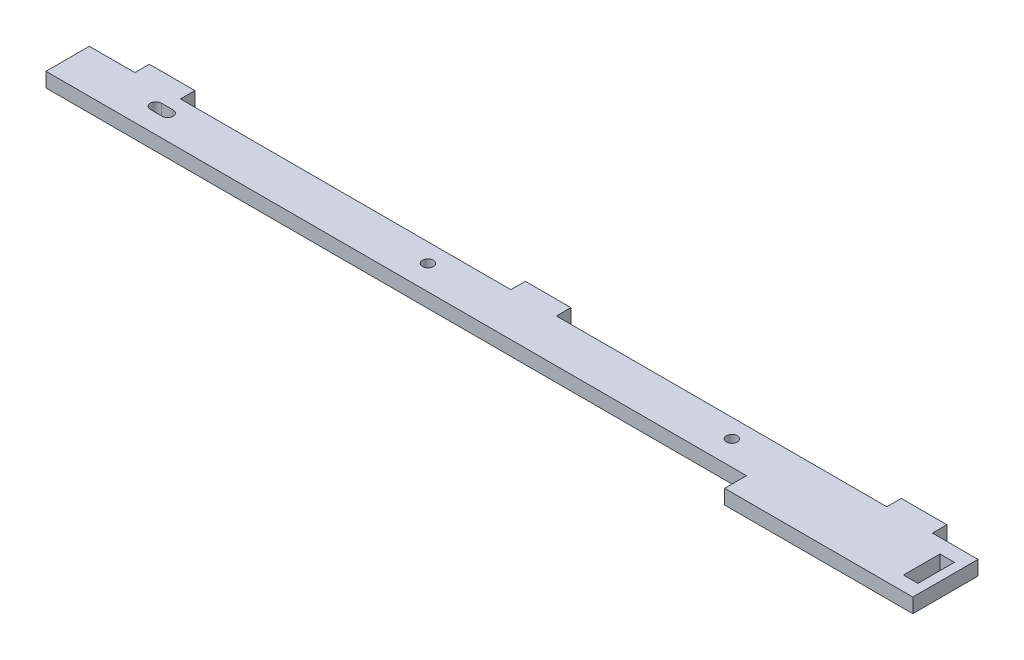
SolidWorks part; units mm, degrees
material "Acrylic (Medium-high impact)"
ref_plane "Front Plane" through (0, 0, 0) normal (0, 0, 1) x (1, 0, 0)
ref_plane "Top Plane" through (0, 0, 0) normal (0, 1, 0) x (1, 0, 0)
ref_plane "Right Plane" through (0, 0, 0) normal (1, 0, 0) x (0, 0, -1)
sketch "Sketch1" plane through (0, 0, 0) normal (0, 1, 0) x (1, 0, 0)
  line L1 (97.5, -4.75) -> (-97.5, -4.75)
  line L2 (97.5, -4.75) -> (97.5, 4.75)
  line L3 (97.5, 4.75) -> (-97.5, 4.75)
  line L4 (-97.5, -4.75) -> (-97.5, 4.75)
  line L5 (97.5, -4.75) -> (-97.5, 4.75) construction
  line L6 (97.5, 4.75) -> (-97.5, -4.75) construction
  point P0 (0, 0)
  dimension "D1" = 9.5
  dimension "D2" = 195
extrude "Boss-Extrude1" add sketch "Sketch1" along normal blind 3.175
hole_wizard "M2 Clearance Hole1" positions "Sketch4" profile "Sketch3" hole size "M2" standard "ANSI Metric" end condition through all
sketch "Sketch4" plane through (0, 3.175, 0) normal (0, 1, 0) x (1, 0, 0)
  line L0 (-77.5, 0.65) -> (47.6, 0.65) construction
  line L2 (-97.5, -4.75) -> (97.5, -4.75) construction
  line L3 (-97.5, 4.75) -> (-97.5, -4.75) construction
  point P0 (-77.5, 0.65)
  point P4 (47.6, 0.65)
  point P11 (-19.1, 0.65)
  dimension "D1" = 5.4
  dimension "D2" = 66.7
  dimension "D3" = 58.4
  dimension "D4" = 20
sketch "Sketch3" plane through (-77.5, 3.175, -0.65) normal (1, 0, 0) x (0, 0, 1)
  line L0 (0, 0) -> (0, 3.175)
  line L1 (0, 3.175) -> (1.2, 3.175)
  line L2 (1.2, 3.175) -> (1.2, 0)
  line L5 (1.2, 0) -> (0, 0)
  line L11 (0, -6.35) -> (0, 107.95) construction
  dimension "Thru Hole Dia." = 2.4
  dimension "Thru Hole Depth" = 3.175
sketch "Sketch5" plane through (0, 0, -4.75) normal (0, 0, -1) x (-1, 0, 0)
  line L0 (-97.5, 0) -> (97.5, 0) construction
  line L1 (87.5, 0) -> (77.5, 0)
  line L2 (87.5, 0) -> (87.5, 3.175)
  line L3 (87.5, 3.175) -> (77.5, 3.175)
  line L4 (77.5, 0) -> (77.5, 3.175)
  line L5 (-97.5, 3.175) -> (97.5, 3.175) construction
  line L6 (97.5, 3.175) -> (97.5, 0) construction
  line L7 (0, 1.7463) -> (0, -1.7463) construction
  line L8 (-87.5, 3.175) -> (-77.5, 3.175)
  line L9 (-77.5, 0) -> (-77.5, 3.175)
  line L10 (-87.5, 0) -> (-77.5, 0)
  line L11 (-87.5, 0) -> (-87.5, 3.175)
  line L13 (5, 0) -> (-5, 0)
  line L14 (5, 0) -> (5, 3.175)
  line L15 (5, 3.175) -> (-5, 3.175)
  line L16 (-5, 0) -> (-5, 3.175)
  dimension "D1" = 10
  dimension "D2" = 10
extrude "Boss-Extrude2" add sketch "Sketch5" along normal blind 3.175
sketch "Sketch6" plane through (0, 0, 4.75) normal (0, 0, 1) x (1, 0, 0)
  line L0 (-97.5, 0) -> (97.5, 0) construction
  line L1 (97.5, 3.175) -> (56.2, 3.175)
  line L2 (97.5, 3.175) -> (97.5, 0)
  line L3 (97.5, 0) -> (56.2, 0)
  line L4 (56.2, 3.175) -> (56.2, 0)
  dimension "D1" = 41.3
extrude "Boss-Extrude3" add sketch "Sketch6" along normal blind 4.8
sketch "Sketch7" plane through (0, 3.175, 0) normal (0, 1, 0) x (1, 0, 0)
  line L0 (97.5, -9.55) -> (97.5, 4.75) construction
  line L1 (92.3, 1.6) -> (95.475, 1.6)
  line L2 (92.3, 1.6) -> (92.3, -6.4)
  line L3 (92.3, -6.4) -> (95.475, -6.4)
  line L4 (95.475, 1.6) -> (95.475, -6.4)
  line L5 (97.5, -2.4) -> (92.3, -2.4) construction
  dimension "D1" = 2.025
  dimension "D2" = 3.175
  dimension "D3" = 8
extrude "Cut-Extrude1" cut sketch "Sketch7" against normal through all
hole_wizard "M2 Clearance Slot1" positions "Sketch8" profile "Sketch9" size "M2" standard "ANSI Metric" slot yes end condition through all
sketch "Sketch8" plane through (0, 3.175, 0) normal (0, 1, 0) x (1, 0, 0)
  line L0 (-80, 0.65) -> (-75, 0.65) construction
  point P0 (-77.5, 0.65)
  dimension "D1" = 5
sketch "Sketch9" plane through (-77.5, 3.175, -0.65) normal (1, 0, 0) x (0, 0, 1)
  line L0 (0, 0) -> (0, 3.175)
  line L1 (0, 3.175) -> (1.2, 3.175)
  line L2 (1.2, 3.175) -> (1.2, 0)
  line L5 (1.2, 0) -> (0, 0)
  line L11 (0, -6.35) -> (0, 107.95) construction
  dimension "Thru Hole Dia." = 2.4
  dimension "Thru Hole Depth" = 3.175
